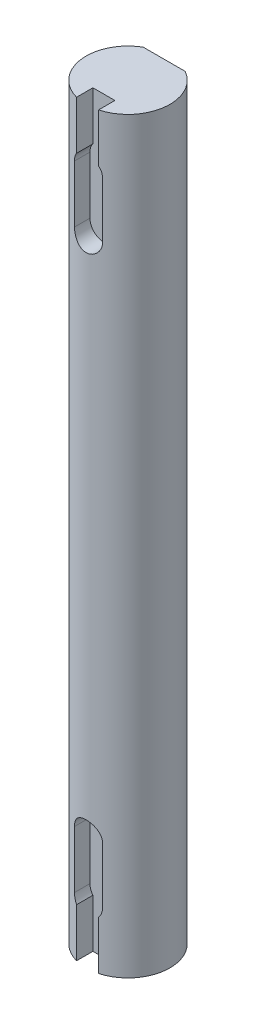
SolidWorks part; units mm, degrees
material "AISI 1045 Steel, cold drawn"
ref_plane "X-Y Datum" through (0, 0, 0) normal (0, 0, 1) x (1, 0, 0)
ref_plane "X-Z Datum" through (0, 0, 0) normal (0, 1, 0) x (1, 0, 0)
ref_plane "Y-Z Datum" through (0, 0, 0) normal (1, 0, 0) x (0, 0, -1)
sketch "Sketch1" plane through (0, 0, 0) normal (0, 1, 0) x (1, 0, 0)
  line L0 (-2.3876, 4.1208) -> (2.3876, 4.1208)
  circle A0 centre (0, 0) radius 4.7625
  dimension "D1" = 9.525
  dimension "D2" = 4.7752
extrude "Boss-Extrude1" add sketch "Sketch1" along normal blind 42.5 and the other way blind 42.5 contours L0 A0 region at (0, 0, 0.1312)
sketch "Sketch2" plane through (0, -42.5, 0) normal (0, -1, 0) x (1, 0, 0)
  line L0 (-1.25, 4.5955) -> (-1.25, 2.7375)
  line L1 (-1.25, 2.7375) -> (1.25, 2.7375)
  line L2 (1.25, 2.7375) -> (1.25, 4.5955)
  arc A0 (2.3876, -4.1208) -> (-2.3876, -4.1208) centre (0, 0) ccw construction
  circle A1 centre (0, 0) radius 4.7625 construction
  point P5 (0, -4.7625)
  point P8 (0, 2.7375)
  dimension "D1" = 2.5
  dimension "D2" = 7.5
extrude "Cut-Extrude1" cut sketch "Sketch2" against normal blind 13 and the other way through all
sketch "Sketch3" plane through (0, 42.5, 0) normal (0, 1, 0) x (1, 0, 0)
  line L0 (-1.25, -4.5955) -> (-1.25, -2.7375)
  line L1 (-1.25, -2.7375) -> (1.25, -2.7375)
  line L2 (1.25, -2.7375) -> (1.25, -4.5955)
  circle A0 centre (0, 0) radius 4.7625 construction
  arc A1 (-1.25, -4.5955) -> (1.25, -4.5955) centre (0, 0) ccw
  point P6 (0, -2.7375)
  point P9 (0, 4.7625)
  dimension "D1" = 2.5
  dimension "D2" = 7.5
extrude "Cut-Extrude2" cut sketch "Sketch3" against normal blind 13
ref_plane "Plane1" through (0, -36, 0) normal (0, -1, 0) x (-1, 0, 0)
sketch "Sketch4" plane through (0, -36, 0) normal (0, -1, 0) x (-1, 0, 0)
  line L0 (-1.25, -2.7375) -> (1.25, -2.7375) construction
  line L1 (-1.5875, -2.7375) -> (1.5875, -2.7375)
  line L2 (-1.5875, -2.7375) -> (-1.5875, -5.2775)
  line L3 (-1.5875, -5.2775) -> (1.5875, -5.2775)
  line L4 (1.5875, -2.7375) -> (1.5875, -5.2775)
  point P6 (3.4039, -2.7375)
  point P7 (0, -2.7375)
  dimension "D1" = 3.175
  dimension "D2" = 2.54
extrude "Cut-Extrude3" cut sketch "Sketch4" against normal up to surface (6.5 mm away) up to face at (0, -29.5, 3.7083)
sketch "Sketch5" plane through (0, 0, 2.7375) normal (0, 0, 1) x (1, 0, 0)
  line L1 (1.25, -36) -> (-1.25, -36) construction
  line L2 (1.5875, -29.5) -> (-1.5875, -29.5) construction
  circle A0 centre (0, -36) radius 1.5875
  circle A1 centre (0, -29.5) radius 1.5875
  dimension "D1" = 3.175
extrude "Cut-Extrude4" cut sketch "Sketch5" along normal through all
sketch "Sketch6" plane through (0, 0, 2.7375) normal (0, 0, 1) x (1, 0, 0)
  line L0 (1.25, 29.5) -> (-1.25, 29.5) construction
  line L1 (0, 36) -> (0, 29.5) construction
  line L2 (1.5875, 29.5) -> (1.5875, 36)
  line L3 (-1.5875, 36) -> (-1.5875, 29.5)
  circle A0 centre (0, 29.5) radius 1.5875
  circle A1 centre (0, 36) radius 1.5875
  point P10 (-1.5875, 29.2961)
  point P11 (-1.5875, 29.5)
  point P12 (-1.5875, 29.5)
  point P13 (0, 0)
  line M5 (-1.25, 42.5) -> (-1.25, 29.5)
  line M6 (-1.25, 29.5) -> (1.25, 29.5)
  line M7 (1.25, 29.5) -> (1.25, 42.5)
  dimension "D1" = 3.175
  dimension "D2" = 6.5
extrude "Cut-Extrude5" cut sketch "Sketch6" along normal through all contours A1 M7 M5 | A0 M7 M6 M5 | A1 L1 A0 M7 | L1 A1 A0 M5 | A1 L3 A0 M5 | A1 A0 L2 M7 | A1 M5 | A1 M7 region at (0.6575, 32.75, 2.7375) region at (-0.6575, 32.75, 2.7375) region at (-0.6775, 34.6092, 2.7375) region at (-1.4271, 32.75, 2.7375) region at (-1.3863, 36, 2.7375) region at (1.3863, 36, 2.7375) region at (1.4271, 32.75, 2.7375) region at (0, 28.9332, 2.7375)
